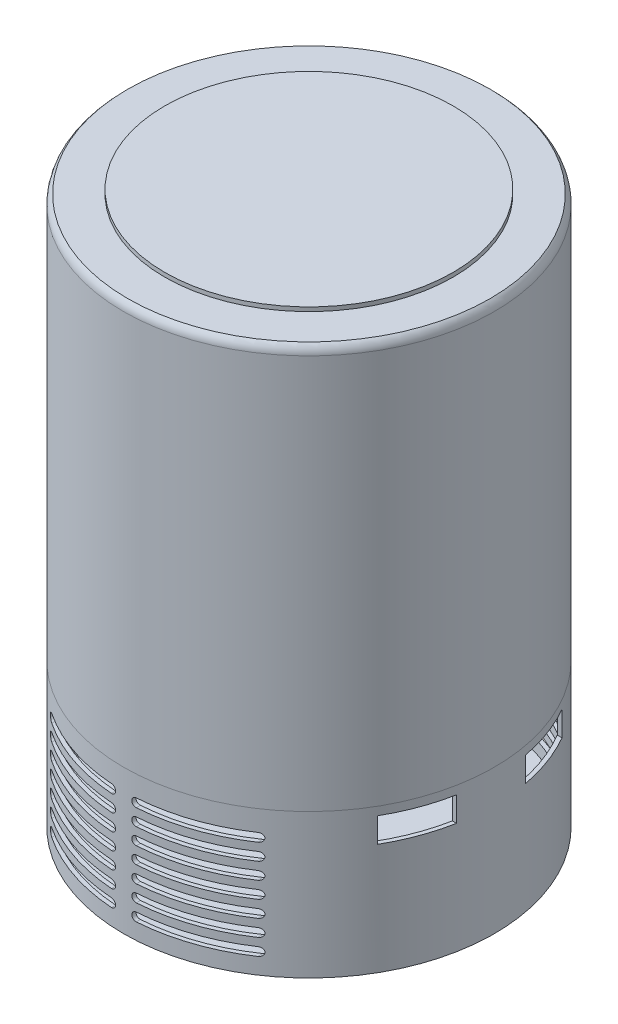
SolidWorks part; units mm, degrees
ref_plane "Front Plane" through (0, 0, 0) normal (0, 0, 1) x (1, 0, 0)
ref_plane "Top Plane" through (0, 0, 0) normal (0, 1, 0) x (1, 0, 0)
ref_plane "Right Plane" through (0, 0, 0) normal (1, 0, 0) x (0, 0, -1)
sketch "Sketch1" plane through (0, 0, 0) normal (0, 1, 0) x (1, 0, 0)
  circle A0 centre (0, 0) radius 45
  circle A1 centre (0, 0) radius 44
  dimension "D1" = 90
  dimension "D2" = 88
extrude "Boss-Extrude1" add sketch "Sketch1" along normal blind 98
fillet "Fillet1" radius 3 1 edges at (0, 98, 45)
sketch "Sketch13" plane through (0, 0, 0) normal (0, 1, 0) x (1, 0, 0)
  circle A0 centre (0, 0) radius 44
  dimension "D1" = 88
extrude "Boss-Extrude9" add sketch "Sketch13" along normal blind 2 from offset 96
sketch "Sketch5" plane through (0, 0, 0) normal (0, 1, 0) x (1, 0, 0)
  circle A0 centre (0, 0) radius 45
  dimension "D1" = 90
extrude "Boss-Extrude6" add sketch "Sketch5" against normal blind 35 separate body
sketch "Sketch6" plane through (0, 0, 0) normal (0, 1, 0) x (1, 0, 0)
  circle A0 centre (0, 0) radius 44
  dimension "D1" = 88
extrude "Cut-Extrude2" cut sketch "Sketch6" against normal blind 34
sketch "Sketch7" plane through (0, 98, 0) normal (0, 1, 0) x (1, 0, 0)
  circle A0 centre (0, 0) radius 35
  dimension "D1" = 70
extrude "Boss-Extrude7" add sketch "Sketch7" along normal blind 1
sketch "Sketch8" plane through (0, 0, 0) normal (1, 0, 0) x (0, 0, -1)
  line L0 (45, -17.5) -> (-47.6224, -17.5) construction
  line L1 (45, -35) -> (45, 0) construction
  line L3 (4, -5.5) -> (-4, -5.5)
  line L4 (4, -5.5) -> (4, -2)
  line L5 (4, -2) -> (-4, -2)
  line L6 (-4, -5.5) -> (-4, -2)
  line L7 (4, -5.5) -> (-4, -2) construction
  line L8 (4, -2) -> (-4, -5.5) construction
  line L10 (44, 0) -> (-44, 0) construction
  point P4 (0, -3.75)
  dimension "D1" = 8
  dimension "D2" = 3.5
  dimension "D3" = 2
extrude "Cut-Extrude3" cut sketch "Sketch8" against normal through all from offset 39 offset against normal yes
sketch "Sketch10" plane through (0, 0, 0) normal (0, 0, 1) x (1, 0, 0)
  line L0 (25, -6.0288) -> (3, -6.0288) construction
  line L5 (0, 12.9357) -> (0, -57.2827) construction
  line L30 (25, -5) -> (3, -5)
  line L31 (25, -7.0576) -> (3, -7.0576)
  line L32 (-25, -6.0288) -> (-3, -6.0288) construction
  line L33 (-25, -5) -> (-3, -5)
  line L34 (-25, -7.0576) -> (-3, -7.0576)
  line L35 (-25, -10.0288) -> (-3, -10.0288) construction
  line L36 (-25, -9) -> (-3, -9)
  line L37 (-25, -11.0576) -> (-3, -11.0576)
  line L38 (25, -10.0288) -> (3, -10.0288) construction
  line L39 (25, -9) -> (3, -9)
  line L40 (25, -11.0576) -> (3, -11.0576)
  line L41 (-25, -14.0288) -> (-3, -14.0288) construction
  line L42 (-25, -13) -> (-3, -13)
  line L43 (-25, -15.0576) -> (-3, -15.0576)
  line L44 (25, -14.0288) -> (3, -14.0288) construction
  line L45 (25, -13) -> (3, -13)
  line L46 (25, -15.0576) -> (3, -15.0576)
  line L47 (-25, -18.0288) -> (-3, -18.0288) construction
  line L48 (-25, -17) -> (-3, -17)
  line L49 (-25, -19.0576) -> (-3, -19.0576)
  line L50 (25, -18.0288) -> (3, -18.0288) construction
  line L51 (25, -17) -> (3, -17)
  line L52 (25, -19.0576) -> (3, -19.0576)
  line L53 (-25, -22.0288) -> (-3, -22.0288) construction
  line L54 (-25, -21) -> (-3, -21)
  line L55 (-25, -23.0576) -> (-3, -23.0576)
  line L56 (25, -22.0288) -> (3, -22.0288) construction
  line L57 (25, -21) -> (3, -21)
  line L58 (25, -23.0576) -> (3, -23.0576)
  line L59 (-25, -26.0288) -> (-3, -26.0288) construction
  line L60 (-25, -25) -> (-3, -25)
  line L61 (-25, -27.0576) -> (-3, -27.0576)
  line L62 (25, -26.0288) -> (3, -26.0288) construction
  line L63 (25, -25) -> (3, -25)
  line L64 (25, -27.0576) -> (3, -27.0576)
  line L65 (45, 0) -> (-45, 0) construction
  line L66 (-25, -30.0288) -> (-3, -30.0288) construction
  line L67 (-25, -29) -> (-3, -29)
  line L68 (-25, -31.0576) -> (-3, -31.0576)
  line L69 (-14, -8.33) -> (-14, -41.8813) construction
  line L70 (25, -30.0288) -> (3, -30.0288) construction
  line L71 (25, -29) -> (3, -29)
  line L72 (25, -31.0576) -> (3, -31.0576)
  arc A0 (-25, -5) -> (-25, -7.0576) centre (-25, -6.0288) ccw
  arc A1 (-3, -7.0576) -> (-3, -5) centre (-3, -6.0288) ccw
  arc A2 (25, -5) -> (25, -7.0576) centre (25, -6.0288) cw
  arc A3 (3, -7.0576) -> (3, -5) centre (3, -6.0288) cw
  arc A4 (-25, -9) -> (-25, -11.0576) centre (-25, -10.0288) ccw
  arc A5 (-3, -11.0576) -> (-3, -9) centre (-3, -10.0288) ccw
  arc A6 (25, -9) -> (25, -11.0576) centre (25, -10.0288) cw
  arc A7 (3, -11.0576) -> (3, -9) centre (3, -10.0288) cw
  arc A8 (-25, -13) -> (-25, -15.0576) centre (-25, -14.0288) ccw
  arc A9 (-3, -15.0576) -> (-3, -13) centre (-3, -14.0288) ccw
  arc A10 (25, -13) -> (25, -15.0576) centre (25, -14.0288) cw
  arc A11 (3, -15.0576) -> (3, -13) centre (3, -14.0288) cw
  arc A12 (-25, -17) -> (-25, -19.0576) centre (-25, -18.0288) ccw
  arc A13 (-3, -19.0576) -> (-3, -17) centre (-3, -18.0288) ccw
  arc A14 (25, -17) -> (25, -19.0576) centre (25, -18.0288) cw
  arc A15 (3, -19.0576) -> (3, -17) centre (3, -18.0288) cw
  arc A16 (-25, -21) -> (-25, -23.0576) centre (-25, -22.0288) ccw
  arc A17 (-3, -23.0576) -> (-3, -21) centre (-3, -22.0288) ccw
  arc A18 (25, -21) -> (25, -23.0576) centre (25, -22.0288) cw
  arc A19 (3, -23.0576) -> (3, -21) centre (3, -22.0288) cw
  arc A20 (-25, -25) -> (-25, -27.0576) centre (-25, -26.0288) ccw
  arc A21 (-3, -27.0576) -> (-3, -25) centre (-3, -26.0288) ccw
  arc A22 (25, -25) -> (25, -27.0576) centre (25, -26.0288) cw
  arc A23 (3, -27.0576) -> (3, -25) centre (3, -26.0288) cw
  arc A24 (-25, -29) -> (-25, -31.0576) centre (-25, -30.0288) ccw
  arc A25 (-3, -31.0576) -> (-3, -29) centre (-3, -30.0288) ccw
  arc A26 (25, -29) -> (25, -31.0576) centre (25, -30.0288) cw
  arc A27 (3, -31.0576) -> (3, -29) centre (3, -30.0288) cw
  point P3 (14, -6.0288)
  point P7 (-14, -6.0288)
  point P19 (14, -10.0288)
  point P22 (-14, -10.0288)
  point P33 (14, -14.0288)
  point P36 (-14, -14.0288)
  point P47 (14, -18.0288)
  point P50 (-14, -18.0288)
  point P61 (14, -22.0288)
  point P64 (-14, -22.0288)
  point P75 (14, -26.0288)
  point P78 (-14, -26.0288)
  point P90 (-14, -30.0288)
  point P97 (0, 0)
  point P98 (0, 0)
  point P101 (14, -30.0288)
  dimension "D1" = 22
  dimension "D2" = 6
  dimension "D3" = 5
  dimension "D5" = 1.9424
  dimension "D4" = 1.9424
extrude "Cut-Extrude5" cut sketch "Sketch10" against normal blind 10 from offset 36 offset against normal yes
sketch "Sketch12" plane through (0, 0, 0) normal (0, 0, 1) x (1, 0, 0)
  line L0 (25, -6.0288) -> (3, -6.0288) construction
  line L5 (0, 12.9357) -> (0, -57.2827) construction
  line L30 (25, -5) -> (3, -5)
  line L31 (25, -7.0576) -> (3, -7.0576)
  line L32 (-25, -6.0288) -> (-3, -6.0288) construction
  line L33 (-25, -5) -> (-3, -5)
  line L34 (-25, -7.0576) -> (-3, -7.0576)
  line L35 (-25, -10.0288) -> (-3, -10.0288) construction
  line L36 (-25, -9) -> (-3, -9)
  line L37 (-25, -11.0576) -> (-3, -11.0576)
  line L38 (25, -10.0288) -> (3, -10.0288) construction
  line L39 (25, -9) -> (3, -9)
  line L40 (25, -11.0576) -> (3, -11.0576)
  line L41 (-25, -14.0288) -> (-3, -14.0288) construction
  line L42 (-25, -13) -> (-3, -13)
  line L43 (-25, -15.0576) -> (-3, -15.0576)
  line L44 (25, -14.0288) -> (3, -14.0288) construction
  line L45 (25, -13) -> (3, -13)
  line L46 (25, -15.0576) -> (3, -15.0576)
  line L47 (-25, -18.0288) -> (-3, -18.0288) construction
  line L48 (-25, -17) -> (-3, -17)
  line L49 (-25, -19.0576) -> (-3, -19.0576)
  line L50 (25, -18.0288) -> (3, -18.0288) construction
  line L51 (25, -17) -> (3, -17)
  line L52 (25, -19.0576) -> (3, -19.0576)
  line L53 (-25, -22.0288) -> (-3, -22.0288) construction
  line L54 (-25, -21) -> (-3, -21)
  line L55 (-25, -23.0576) -> (-3, -23.0576)
  line L56 (25, -22.0288) -> (3, -22.0288) construction
  line L57 (25, -21) -> (3, -21)
  line L58 (25, -23.0576) -> (3, -23.0576)
  line L59 (-25, -26.0288) -> (-3, -26.0288) construction
  line L60 (-25, -25) -> (-3, -25)
  line L61 (-25, -27.0576) -> (-3, -27.0576)
  line L62 (25, -26.0288) -> (3, -26.0288) construction
  line L63 (25, -25) -> (3, -25)
  line L64 (25, -27.0576) -> (3, -27.0576)
  line L65 (45, 0) -> (-45, 0) construction
  line L66 (-25, -29) -> (-3, -29) construction
  line L67 (-25, -29) -> (-3, -29)
  line L68 (-25, -31.0576) -> (-3, -31.0576) construction
  line L69 (-25, -31.0576) -> (-3, -31.0576)
  line L70 (25, -31.0576) -> (3, -31.0576) construction
  line L71 (25, -29) -> (3, -29) construction
  line L72 (25, -31.0576) -> (3, -31.0576)
  line L73 (25, -29) -> (3, -29)
  arc A0 (-25, -5) -> (-25, -7.0576) centre (-25, -6.0288) ccw
  arc A1 (-3, -7.0576) -> (-3, -5) centre (-3, -6.0288) ccw
  arc A2 (25, -5) -> (25, -7.0576) centre (25, -6.0288) cw
  arc A3 (3, -7.0576) -> (3, -5) centre (3, -6.0288) cw
  arc A4 (-25, -9) -> (-25, -11.0576) centre (-25, -10.0288) ccw
  arc A5 (-3, -11.0576) -> (-3, -9) centre (-3, -10.0288) ccw
  arc A6 (25, -9) -> (25, -11.0576) centre (25, -10.0288) cw
  arc A7 (3, -11.0576) -> (3, -9) centre (3, -10.0288) cw
  arc A8 (-25, -13) -> (-25, -15.0576) centre (-25, -14.0288) ccw
  arc A9 (-3, -15.0576) -> (-3, -13) centre (-3, -14.0288) ccw
  arc A10 (25, -13) -> (25, -15.0576) centre (25, -14.0288) cw
  arc A11 (3, -15.0576) -> (3, -13) centre (3, -14.0288) cw
  arc A12 (-25, -17) -> (-25, -19.0576) centre (-25, -18.0288) ccw
  arc A13 (-3, -19.0576) -> (-3, -17) centre (-3, -18.0288) ccw
  arc A14 (25, -17) -> (25, -19.0576) centre (25, -18.0288) cw
  arc A15 (3, -19.0576) -> (3, -17) centre (3, -18.0288) cw
  arc A16 (-25, -21) -> (-25, -23.0576) centre (-25, -22.0288) ccw
  arc A17 (-3, -23.0576) -> (-3, -21) centre (-3, -22.0288) ccw
  arc A18 (25, -21) -> (25, -23.0576) centre (25, -22.0288) cw
  arc A19 (3, -23.0576) -> (3, -21) centre (3, -22.0288) cw
  arc A20 (-25, -25) -> (-25, -27.0576) centre (-25, -26.0288) ccw
  arc A21 (-3, -27.0576) -> (-3, -25) centre (-3, -26.0288) ccw
  arc A22 (25, -25) -> (25, -27.0576) centre (25, -26.0288) cw
  arc A23 (3, -27.0576) -> (3, -25) centre (3, -26.0288) cw
  arc A24 (-3, -31.0576) -> (-3, -29) centre (-3, -30.0288) ccw construction
  arc A25 (-25, -29) -> (-25, -31.0576) centre (-25, -30.0288) ccw construction
  arc A26 (-3, -31.0576) -> (-3, -29) centre (-3, -30.0288) ccw
  arc A27 (-25, -29) -> (-25, -31.0576) centre (-25, -30.0288) ccw
  arc A28 (25, -31.0576) -> (25, -29) centre (25, -30.0288) ccw construction
  arc A29 (3, -29) -> (3, -31.0576) centre (3, -30.0288) ccw construction
  arc A30 (25, -31.0576) -> (25, -29) centre (25, -30.0288) ccw
  arc A31 (3, -29) -> (3, -31.0576) centre (3, -30.0288) ccw
  point P3 (14, -6.0288)
  point P7 (-14, -6.0288)
  point P19 (14, -10.0288)
  point P22 (-14, -10.0288)
  point P33 (14, -14.0288)
  point P36 (-14, -14.0288)
  point P47 (14, -18.0288)
  point P50 (-14, -18.0288)
  point P61 (14, -22.0288)
  point P64 (-14, -22.0288)
  point P75 (14, -26.0288)
  point P78 (-14, -26.0288)
  dimension "D1" = 22
  dimension "D2" = 6
  dimension "D3" = 5
extrude "Cut-Extrude6" cut sketch "Sketch12" against normal blind 10 from offset 46
sketch "Sketch15" [suppressed] plane through (0, 0, 0) normal (0, 1, 0) x (1, 0, 0)
  line L0 (-48.3245, 0) -> (49.2947, 0) construction
  line L1 (0, 0) -> (42.2862, -15.3909)
  line L2 (0, 0) -> (42.2862, 15.3909)
  circle A0 centre (0, 0) radius 45 construction
  dimension "D1" = 20
sketch "Sketch14" plane through (0, 0, 0) normal (1, 0, 0) x (0, 0, -1)
  line L0 (-47.6224, -17.5) -> (48.7265, -17.5) construction
  line L2 (-8.3909, -8) -> (-22.3909, -8)
  line L3 (-8.3909, -8) -> (-8.3909, -2)
  line L4 (-8.3909, -2) -> (-22.3909, -2)
  line L5 (-22.3909, -8) -> (-22.3909, -2)
  line L6 (-8.3909, -8) -> (-22.3909, -2) construction
  line L7 (-8.3909, -2) -> (-22.3909, -8) construction
  line L8 (22.3909, -8) -> (8.3909, -8)
  line L9 (22.3909, -8) -> (22.3909, -2)
  line L10 (22.3909, -2) -> (8.3909, -2)
  line L11 (8.3909, -8) -> (8.3909, -2)
  line L12 (22.3909, -8) -> (8.3909, -2) construction
  line L13 (22.3909, -2) -> (8.3909, -8) construction
  line L16 (-44, 0) -> (44, 0) construction
  line L17 (0, 16.6073) -> (0, -22.4392) construction
  line L19 (-15.3909, 7.2444) -> (-15.3909, -11.5076) construction
  line L20 (15.3909, 7.2444) -> (15.3909, -11.5076) construction
  point P3 (-15.3909, -5)
  point P8 (15.3909, -5)
  point P13 (0, 0)
  point P14 (0, 0)
  point P15 (0, 0)
  point P26 (-15.3909, -2)
  point P27 (0, 0)
  dimension "D1" = 14
  dimension "D2" = 6
  dimension "D3" = 14
  dimension "D4" = 6
  dimension "D7" = 2
  dimension "D8" = 2
extrude "Cut-Extrude7" cut sketch "Sketch14" along normal blind 10 from offset 36
